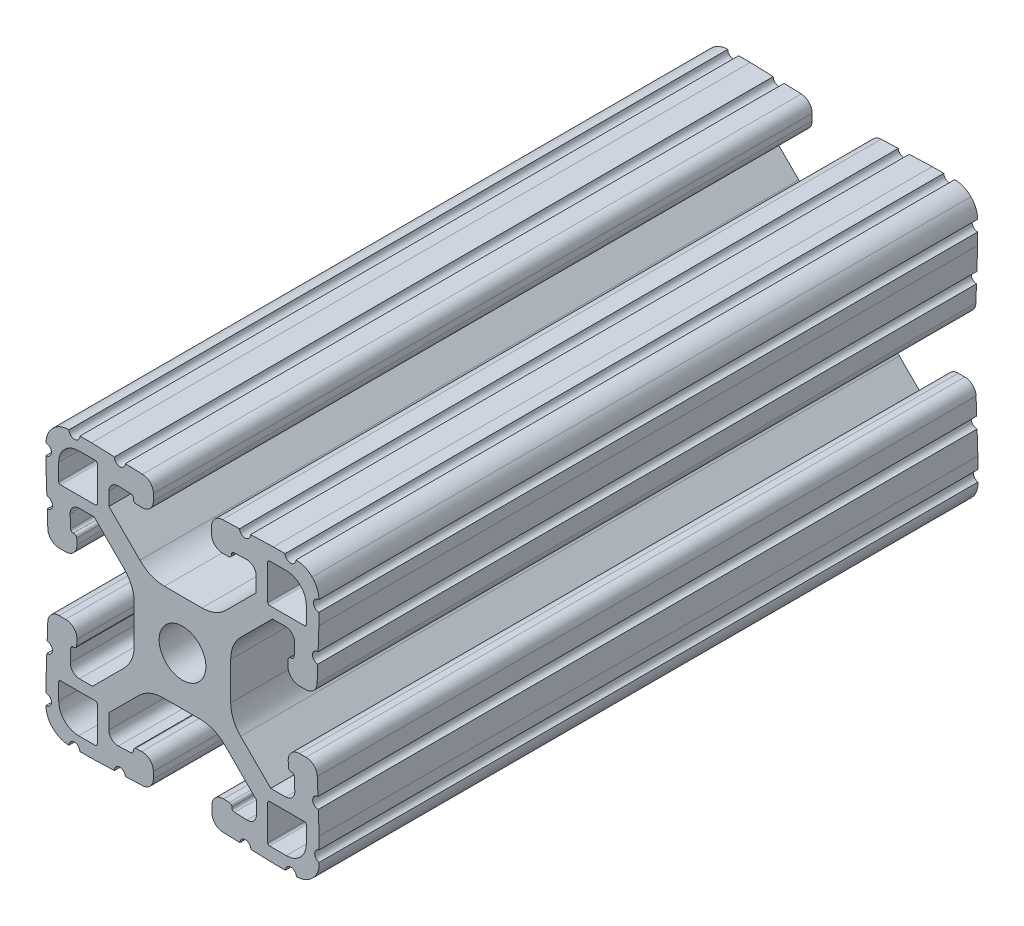
SolidWorks part; units mm, degrees
material "6061-T6 (SS)"
ref_plane "Front Plane" through (0, 0, 0) normal (0, 0, 1) x (1, 0, 0)
ref_plane "Top Plane" through (0, 0, 0) normal (0, 1, 0) x (1, 0, 0)
ref_plane "Right Plane" through (0, 0, 0) normal (1, 0, 0) x (0, 0, -1)
ref_plane "Plane1" through (0, 0, -25.4) normal (0, 0, -1) x (-1, 0, 0)
sketch "Sketch1" plane through (0, 0, -25.4) normal (0, 0, -1) x (-1, 0, 0)
  line L0 (-83.3577, 88.2941) -> (-83.3577, 93.1709)
  line L1 (-83.1037, 93.4249) -> (-80.767, 93.4249)
  line L2 (-77.9729, 90.6309) -> (-77.9729, 88.2941)
  line L3 (-78.2269, 88.0401) -> (-83.1037, 88.0401)
  line L4 (-83.3577, 59.2291) -> (-83.3577, 64.1059)
  line L5 (-83.1037, 64.3599) -> (-78.2269, 64.3599)
  line L6 (-77.9729, 64.1059) -> (-77.9729, 61.7691)
  line L7 (-80.767, 58.9751) -> (-83.1037, 58.9751)
  line L8 (-107.1423, 93.1709) -> (-107.1423, 88.2941)
  line L9 (-107.3963, 88.0401) -> (-112.2731, 88.0401)
  line L10 (-112.5271, 88.2941) -> (-112.5271, 90.6309)
  line L11 (-109.733, 93.4249) -> (-107.3963, 93.4249)
  line L12 (-107.1423, 64.1059) -> (-107.1423, 59.2291)
  line L13 (-107.3963, 58.9751) -> (-109.733, 58.9751)
  line L14 (-112.5271, 61.7691) -> (-112.5271, 64.1059)
  line L15 (-112.2731, 64.3599) -> (-107.3963, 64.3599)
  line L16 (-88.0437, 91.8626) -> (-86.2967, 91.9236)
  line L17 (-84.9824, 90.6544) -> (-84.9824, 88.8002)
  line L18 (-84.9824, 88.8002) -> (-89.3066, 84.476)
  line L19 (-92.7196, 83.0295) -> (-97.9616, 83.0295)
  line L20 (-101.3202, 84.4207) -> (-105.516, 88.6165)
  line L21 (-105.516, 88.6165) -> (-105.516, 90.7313)
  line L22 (-104.2017, 92.0006) -> (-102.4547, 91.9396)
  line L23 (-101.7262, 91.1059) -> (-100.9297, 91.0781)
  line L24 (-99.2999, 92.6519) -> (-99.2999, 93.5668)
  line L25 (-100.8197, 95.1407) -> (-103.2119, 95.2242)
  line L26 (-104.735, 95.2774) -> (-107.9359, 95.3892)
  line L27 (-107.9359, 95.3892) -> (-109.5615, 95.3892)
  line L28 (-114.2859, 90.6648) -> (-114.2859, 89.0392)
  line L29 (-114.2859, 89.0392) -> (-114.1741, 85.8383)
  line L30 (-114.1209, 84.3152) -> (-114.0374, 81.9231)
  line L31 (-112.4635, 80.4032) -> (-111.5486, 80.4032)
  line L32 (-109.9748, 82.033) -> (-110.0026, 82.8295)
  line L33 (-110.8377, 83.5577) -> (-110.8987, 85.3047)
  line L34 (-109.6294, 86.619) -> (-107.8072, 86.619)
  line L35 (-107.8072, 86.619) -> (-103.3649, 82.1768)
  line L36 (-101.9737, 78.8182) -> (-101.9737, 73.576)
  line L37 (-103.3649, 70.2174) -> (-107.5607, 66.0217)
  line L38 (-107.5607, 66.0217) -> (-109.6524, 66.0217)
  line L39 (-110.9217, 67.336) -> (-110.8607, 69.083)
  line L40 (-110.0322, 69.8124) -> (-110.0043, 70.6089)
  line L41 (-111.5782, 72.2387) -> (-112.4931, 72.2387)
  line L42 (-114.0669, 70.7189) -> (-114.1505, 68.3267)
  line L43 (-114.2036, 66.8036) -> (-114.3154, 63.6027)
  line L44 (-114.3154, 63.6027) -> (-114.3154, 61.9626)
  line L45 (-109.6111, 57.1437) -> (-107.9855, 57.1437)
  line L46 (-107.9855, 57.1437) -> (-104.7846, 57.2555)
  line L47 (-103.2615, 57.3086) -> (-100.8694, 57.3922)
  line L48 (-99.3495, 58.966) -> (-99.3495, 59.8809)
  line L49 (-100.9794, 61.4548) -> (-101.7758, 61.4269)
  line L50 (-102.5054, 60.599) -> (-104.2524, 60.538)
  line L51 (-105.5667, 61.8072) -> (-105.5667, 63.6295)
  line L52 (-105.5667, 63.6295) -> (-101.1311, 68.065)
  line L53 (-97.7725, 69.4562) -> (-92.5304, 69.4562)
  line L54 (-89.1717, 68.065) -> (-84.976, 63.8692)
  line L55 (-84.976, 63.8692) -> (-84.976, 61.7811)
  line L56 (-86.2903, 60.5118) -> (-88.0373, 60.5728)
  line L57 (-88.7596, 61.4332) -> (-89.5561, 61.461)
  line L58 (-91.1859, 59.8872) -> (-91.1859, 58.9723)
  line L59 (-89.6661, 57.3985) -> (-87.2739, 57.3149)
  line L60 (-85.7508, 57.2617) -> (-82.5499, 57.15)
  line L61 (-82.5499, 57.15) -> (-80.9244, 57.15)
  line L62 (-76.2, 61.8744) -> (-76.2, 63.4999)
  line L63 (-76.2, 63.4999) -> (-76.3117, 66.7008)
  line L64 (-76.3649, 68.2239) -> (-76.4484, 70.6161)
  line L65 (-78.0223, 72.1359) -> (-78.9372, 72.1359)
  line L66 (-80.511, 70.5061) -> (-80.4832, 69.7096)
  line L67 (-79.6552, 68.9801) -> (-79.5942, 67.2331)
  line L68 (-80.8634, 65.9188) -> (-82.6857, 65.9188)
  line L69 (-82.6857, 65.9188) -> (-87.1213, 70.3543)
  line L70 (-88.5125, 73.7128) -> (-88.5126, 78.955)
  line L71 (-87.1214, 82.3137) -> (-82.9257, 86.5095)
  line L72 (-82.9257, 86.5095) -> (-80.8375, 86.5095)
  line L73 (-79.5682, 85.1951) -> (-79.6293, 83.4482)
  line L74 (-80.4896, 82.7258) -> (-80.5175, 81.9294)
  line L75 (-78.9436, 80.2995) -> (-78.0287, 80.2995)
  line L76 (-76.4549, 81.8194) -> (-76.3713, 84.2115)
  line L77 (-76.3182, 85.7346) -> (-76.2064, 88.9355)
  line L78 (-76.2064, 88.9355) -> (-76.2064, 90.5611)
  line L79 (-80.9308, 95.2855) -> (-82.5564, 95.2855)
  line L80 (-82.5564, 95.2855) -> (-85.7573, 95.1737)
  line L81 (-87.2803, 95.1205) -> (-89.6725, 95.037)
  line L82 (-91.1924, 93.4632) -> (-91.1924, 92.5483)
  line L83 (-89.5625, 90.9744) -> (-88.7661, 91.0023)
  arc A0 (-83.3577, 93.1709) -> (-83.1037, 93.4249) centre (-83.1037, 93.1709) cw
  arc A1 (-80.767, 93.4249) -> (-77.9729, 90.6309) centre (-80.7669, 90.6309) cw
  arc A2 (-77.9729, 88.2941) -> (-78.2269, 88.0401) centre (-78.2269, 88.2941) cw
  arc A3 (-83.1037, 88.0401) -> (-83.3577, 88.2941) centre (-83.1037, 88.2941) cw
  arc A4 (-83.1037, 58.9751) -> (-83.3577, 59.2291) centre (-83.1037, 59.2291) cw
  arc A5 (-83.3577, 64.1059) -> (-83.1037, 64.3599) centre (-83.1037, 64.1059) cw
  arc A6 (-78.2269, 64.3599) -> (-77.9729, 64.1059) centre (-78.2269, 64.1059) cw
  arc A7 (-77.9729, 61.7691) -> (-80.767, 58.9751) centre (-80.7669, 61.7691) cw
  arc A8 (-107.3963, 93.4249) -> (-107.1423, 93.1709) centre (-107.3963, 93.1709) cw
  arc A9 (-107.1423, 88.2941) -> (-107.3963, 88.0401) centre (-107.3963, 88.2941) cw
  arc A10 (-112.2731, 88.0401) -> (-112.5271, 88.2941) centre (-112.2731, 88.2941) cw
  arc A11 (-112.5271, 90.6309) -> (-109.733, 93.4249) centre (-109.7331, 90.6309) cw
  arc A12 (-107.1423, 59.2291) -> (-107.3963, 58.9751) centre (-107.3963, 59.2291) cw
  arc A13 (-109.733, 58.9751) -> (-112.5271, 61.7691) centre (-109.7331, 61.7691) cw
  arc A14 (-112.5271, 64.1059) -> (-112.2731, 64.3599) centre (-112.2731, 64.1059) cw
  arc A15 (-107.3963, 64.3599) -> (-107.1423, 64.1059) centre (-107.3963, 64.1059) cw
  circle A16 centre (-95.25, 76.2) radius 3.2639
  arc A17 (-88.7661, 91.0023) -> (-88.3984, 91.383) centre (-88.7794, 91.383) ccw
  arc A18 (-88.3984, 91.383) -> (-88.0437, 91.8626) centre (-88.0304, 91.4819) cw
  arc A19 (-86.2967, 91.9236) -> (-84.9824, 90.6544) centre (-86.2524, 90.6544) cw
  arc A20 (-89.3066, 84.476) -> (-92.7196, 83.0295) centre (-92.7196, 87.7793) cw
  arc A21 (-97.9616, 83.0295) -> (-101.3202, 84.4207) centre (-97.9616, 87.7793) cw
  arc A22 (-105.516, 90.7313) -> (-104.2017, 92.0006) centre (-104.246, 90.7313) cw
  arc A23 (-102.4547, 91.9396) -> (-102.087, 91.5588) centre (-102.468, 91.5588) cw
  arc A24 (-102.087, 91.5588) -> (-101.7262, 91.1059) centre (-101.7129, 91.4867) ccw
  arc A25 (-100.9297, 91.0781) -> (-99.2999, 92.6519) centre (-100.8747, 92.6519) ccw
  arc A26 (-99.2999, 93.5668) -> (-100.8197, 95.1407) centre (-100.8747, 93.5668) ccw
  arc A27 (-103.2119, 95.2242) -> (-104.735, 95.2774) centre (-103.9735, 95.2508) cw
  arc A28 (-109.5615, 95.3892) -> (-111.0855, 95.3892) centre (-110.3235, 95.3892) cw
  arc A29 (-111.0855, 95.3892) -> (-113.3432, 94.4465) centre (-111.0855, 92.2142) ccw
  arc A30 (-113.3432, 94.4465) -> (-114.2859, 92.1888) centre (-111.1109, 92.1888) ccw
  arc A31 (-114.2859, 92.1888) -> (-114.2859, 90.6648) centre (-114.2859, 91.4268) cw
  arc A32 (-114.1741, 85.8383) -> (-114.1209, 84.3152) centre (-114.1475, 85.0768) cw
  arc A33 (-114.0374, 81.9231) -> (-112.4635, 80.4032) centre (-112.4635, 81.978) ccw
  arc A34 (-111.5486, 80.4032) -> (-109.9748, 82.033) centre (-111.5486, 81.978) ccw
  arc A35 (-110.0026, 82.8295) -> (-110.3834, 83.1972) centre (-110.3834, 82.8162) ccw
  arc A36 (-110.3834, 83.1972) -> (-110.8377, 83.5577) centre (-110.4569, 83.571) cw
  arc A37 (-110.8987, 85.3047) -> (-109.6294, 86.619) centre (-109.6294, 85.349) cw
  arc A38 (-103.3649, 82.1768) -> (-101.9737, 78.8182) centre (-106.7235, 78.8182) cw
  arc A39 (-101.9737, 73.576) -> (-103.3649, 70.2174) centre (-106.7235, 73.576) cw
  arc A40 (-109.6524, 66.0217) -> (-110.9217, 67.336) centre (-109.6524, 67.2917) cw
  arc A41 (-110.8607, 69.083) -> (-110.4799, 69.4507) centre (-110.4799, 69.0697) cw
  arc A42 (-110.4799, 69.4507) -> (-110.0322, 69.8124) centre (-110.413, 69.8257) ccw
  arc A43 (-110.0043, 70.6089) -> (-111.5782, 72.2387) centre (-111.5782, 70.6639) ccw
  arc A44 (-112.4931, 72.2387) -> (-114.0669, 70.7189) centre (-112.4931, 70.6639) ccw
  arc A45 (-114.1505, 68.3267) -> (-114.2036, 66.8036) centre (-114.1771, 67.5652) cw
  arc A46 (-114.3154, 61.9626) -> (-114.3332, 60.4644) centre (-114.4639, 61.2152) cw
  arc A47 (-114.3332, 60.4644) -> (-113.3928, 58.0864) centre (-111.1605, 60.3441) ccw
  arc A48 (-113.3928, 58.0864) -> (-111.1351, 57.1437) centre (-111.1351, 60.3187) ccw
  arc A49 (-111.1351, 57.1437) -> (-109.6111, 57.1437) centre (-110.3731, 57.1437) cw
  arc A50 (-104.7846, 57.2555) -> (-103.2615, 57.3086) centre (-104.0231, 57.2821) cw
  arc A51 (-100.8694, 57.3922) -> (-99.3495, 58.966) centre (-100.9243, 58.966) ccw
  arc A52 (-99.3495, 59.8809) -> (-100.9794, 61.4548) centre (-100.9243, 59.8809) ccw
  arc A53 (-101.7758, 61.4269) -> (-102.1435, 61.0462) centre (-101.7625, 61.0462) ccw
  arc A54 (-102.1435, 61.0462) -> (-102.5054, 60.599) centre (-102.5187, 60.9797) cw
  arc A55 (-104.2524, 60.538) -> (-105.5667, 61.8072) centre (-104.2967, 61.8072) cw
  arc A56 (-101.1311, 68.065) -> (-97.7725, 69.4562) centre (-97.7725, 64.7064) cw
  arc A57 (-92.5304, 69.4562) -> (-89.1717, 68.065) centre (-92.5304, 64.7064) cw
  arc A58 (-84.976, 61.7811) -> (-86.2903, 60.5118) centre (-86.246, 61.7811) cw
  arc A59 (-88.0373, 60.5728) -> (-88.405, 60.9536) centre (-88.024, 60.9536) cw
  arc A60 (-88.405, 60.9536) -> (-88.7596, 61.4332) centre (-88.7729, 61.0524) ccw
  arc A61 (-89.5561, 61.461) -> (-91.1859, 59.8872) centre (-89.6111, 59.8872) ccw
  arc A62 (-91.1859, 58.9723) -> (-89.6661, 57.3985) centre (-89.6111, 58.9723) ccw
  arc A63 (-87.2739, 57.3149) -> (-85.7508, 57.2617) centre (-86.5124, 57.2883) cw
  arc A64 (-80.9244, 57.15) -> (-79.4004, 57.15) centre (-80.1624, 57.15) cw
  arc A65 (-79.4004, 57.15) -> (-77.1426, 58.0927) centre (-79.4004, 60.325) ccw
  arc A66 (-77.1426, 58.0927) -> (-76.2, 60.3504) centre (-79.375, 60.3504) ccw
  arc A67 (-76.2, 60.3504) -> (-76.2, 61.8744) centre (-76.2, 61.1124) cw
  arc A68 (-76.3117, 66.7008) -> (-76.3649, 68.2239) centre (-76.3383, 67.4624) cw
  arc A69 (-76.4484, 70.6161) -> (-78.0223, 72.1359) centre (-78.0223, 70.5611) ccw
  arc A70 (-78.9372, 72.1359) -> (-80.511, 70.5061) centre (-78.9372, 70.5611) ccw
  arc A71 (-80.4832, 69.7096) -> (-80.1024, 69.342) centre (-80.1024, 69.723) ccw
  arc A72 (-80.1024, 69.342) -> (-79.6552, 68.9801) centre (-80.036, 68.9668) cw
  arc A73 (-79.5942, 67.2331) -> (-80.8634, 65.9188) centre (-80.8634, 67.1888) cw
  arc A74 (-87.1213, 70.3543) -> (-88.5125, 73.7128) centre (-83.7627, 73.7129) cw
  arc A75 (-88.5126, 78.955) -> (-87.1214, 82.3137) centre (-83.7628, 78.9551) cw
  arc A76 (-80.8375, 86.5095) -> (-79.5682, 85.1951) centre (-80.8375, 85.2395) cw
  arc A77 (-79.6293, 83.4482) -> (-80.01, 83.0805) centre (-80.01, 83.4615) cw
  arc A78 (-80.01, 83.0805) -> (-80.4896, 82.7258) centre (-80.1089, 82.7125) ccw
  arc A79 (-80.5175, 81.9294) -> (-78.9436, 80.2995) centre (-78.9436, 81.8743) ccw
  arc A80 (-78.0287, 80.2995) -> (-76.4549, 81.8194) centre (-78.0287, 81.8743) ccw
  arc A81 (-76.3713, 84.2115) -> (-76.3182, 85.7346) centre (-76.3448, 84.9731) cw
  arc A82 (-76.2064, 90.5611) -> (-76.2064, 92.0851) centre (-76.2064, 91.3231) cw
  arc A83 (-76.2064, 92.0851) -> (-77.1491, 94.3428) centre (-79.3814, 92.0851) ccw
  arc A84 (-77.1491, 94.3428) -> (-79.4068, 95.2855) centre (-79.4068, 92.1105) ccw
  arc A85 (-79.4068, 95.2855) -> (-80.9308, 95.2855) centre (-80.1688, 95.2855) cw
  arc A86 (-85.7573, 95.1737) -> (-87.2803, 95.1205) centre (-86.5188, 95.1471) cw
  arc A87 (-89.6725, 95.037) -> (-91.1924, 93.4632) centre (-89.6176, 93.4632) ccw
  arc A88 (-91.1924, 92.5483) -> (-89.5625, 90.9744) centre (-89.6176, 92.5483) ccw
extrude "Boss-Extrude1" add sketch "Sketch1" against normal blind 91.9353
